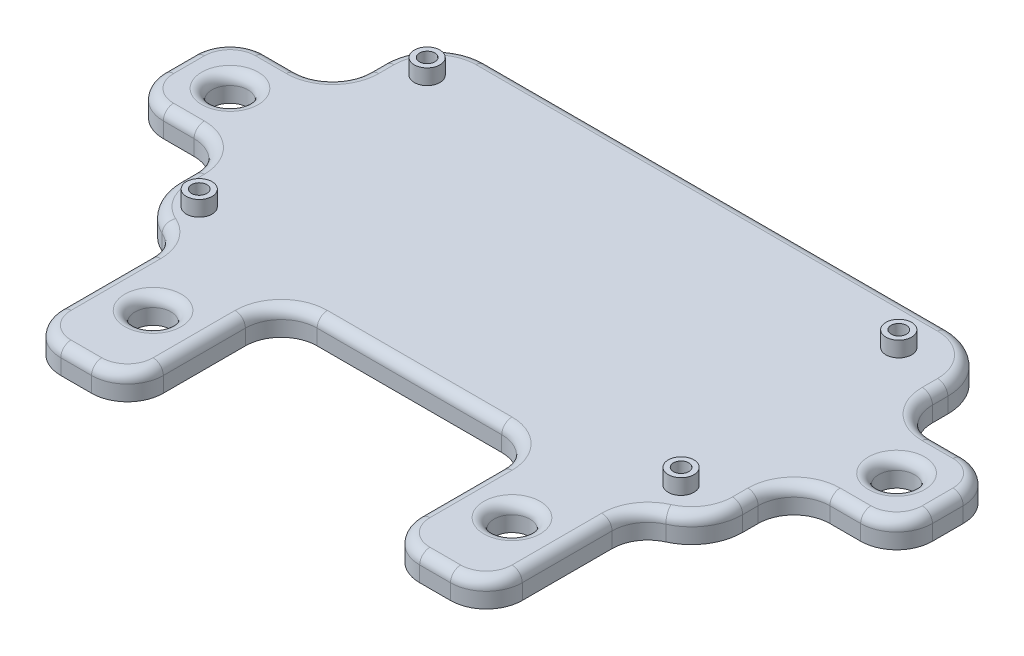
SolidWorks part; units mm, degrees
ref_plane "Front Plane" through (0, 0, 0) normal (0, 0, 1) x (1, 0, 0)
ref_plane "Top Plane" through (0, 0, 0) normal (0, 1, 0) x (1, 0, 0)
ref_plane "Right Plane" through (0, 0, 0) normal (1, 0, 0) x (0, 0, -1)
sketch "Sketch1" plane through (0, 0, 0) normal (0, 1, 0) x (1, 0, 0)
  line L1 (-49.43, 40.0745) -> (60.57, 40.0745)
  line L2 (-49.43, 40.0745) -> (-49.43, -19.9255)
  line L3 (-49.43, -19.9255) -> (60.57, -19.9255)
  line L4 (60.57, 40.0745) -> (60.57, -19.9255)
  dimension "D1" = 60
  dimension "D2" = 110
extrude "Boss-Extrude1" add sketch "Sketch1" along normal blind 5
sketch "Sketch2" plane through (0, 5, 0) normal (0, 1, 0) x (1, 0, 0)
  line L0 (-49.43, -19.9255) -> (60.57, -19.9255) construction
  line L1 (-49.43, 40.0745) -> (-49.43, -19.9255) construction
  circle A0 centre (-42.43, 31.5245) radius 1.0922
  circle A1 centre (-42.43, -12.9255) radius 1.0922
  circle A2 centre (51.55, -12.9255) radius 1.0922
  circle A3 centre (49.55, 31.5245) radius 1.0922
  dimension "D4" = 2.1844
  dimension "D5" = 93.98
  dimension "D1" = 44.45
  dimension "D2" = 7
  dimension "D3" = 7
extrude "Cut-Extrude1" cut sketch "Sketch2" against normal blind 10
sketch "Sketch3" plane through (0, 5, 0) normal (0, 1, 0) x (1, 0, 0)
  circle A0 centre (-42.43, 31.5245) radius 2.5
  circle A1 centre (-42.43, -12.9255) radius 2.5
  circle A2 centre (51.55, -12.9255) radius 2.5
  circle A3 centre (49.55, 31.5245) radius 2.5
  dimension "D1" = 5
extrude "Boss-Extrude2" add sketch "Sketch3" along normal blind 3
sketch "Sketch4" plane through (0, 8, 0) normal (0, 1, 0) x (1, 0, 0)
  circle A0 centre (-42.43, 31.5245) radius 1.5
  circle A1 centre (49.55, 31.5245) radius 1.5
  circle A2 centre (51.55, -12.9255) radius 1.5
  circle A3 centre (-42.43, -12.9255) radius 1.5
  dimension "D1" = 3
extrude "Cut-Extrude2" cut sketch "Sketch4" against normal blind 3
sketch "Sketch5" plane through (60.57, 0, 0) normal (1, 0, 0) x (0, 0, -1)
  line L0 (10.0745, 5) -> (10.0745, 0) construction
  line L1 (-19.9255, 5) -> (40.0745, 5) construction
  line L2 (-19.9255, 0) -> (40.0745, 0) construction
  line L4 (0.0745, 5) -> (20.0745, 5)
  line L5 (0.0745, 5) -> (0.0745, 0)
  line L6 (0.0745, 0) -> (20.0745, 0)
  line L7 (20.0745, 5) -> (20.0745, 0)
  line L8 (0.0745, 5) -> (20.0745, 0) construction
  line L9 (0.0745, 0) -> (20.0745, 5) construction
  point P6 (10.0745, 2.5)
  dimension "D1" = 20
extrude "Boss-Extrude3" add sketch "Sketch5" along normal blind 20 and the other way blind 130
sketch "Sketch6" plane through (0, 5, 0) normal (0, 1, 0) x (1, 0, 0)
  line L0 (-69.43, 10.0745) -> (80.57, 10.0745) construction
  line L1 (-69.43, 20.0745) -> (-69.43, 0.0745) construction
  line L2 (80.57, 20.0745) -> (80.57, 0.0745) construction
  circle A0 centre (-59.43, 10.0745) radius 3.5
  circle A1 centre (70.57, 10.0745) radius 3.5
  dimension "D3" = 7
  dimension "D1" = 10
  dimension "D2" = 10
extrude "Cut-Extrude3" cut sketch "Sketch6" against normal blind 20
sketch "Sketch7" plane through (0, 0, 19.9255) normal (0, 0, 1) x (1, 0, 0)
  line L0 (-49.43, 2.5) -> (60.57, 2.5) construction
  line L1 (-49.43, 5) -> (-49.43, 0) construction
  line L2 (60.57, 5) -> (60.57, 0) construction
  line L3 (5.57, 5) -> (5.57, 0) construction
  line L4 (-49.43, 5) -> (60.57, 5) construction
  line L5 (-49.43, 0) -> (60.57, 0) construction
  line L7 (-39.43, 5) -> (-19.43, 5)
  line L8 (-39.43, 5) -> (-39.43, 0)
  line L9 (-39.43, 0) -> (-19.43, 0)
  line L10 (-19.43, 5) -> (-19.43, 0)
  line L11 (-39.43, 5) -> (-19.43, 0) construction
  line L12 (-39.43, 0) -> (-19.43, 5) construction
  line L13 (30.57, 5) -> (50.57, 5)
  line L14 (30.57, 5) -> (30.57, 0)
  line L15 (30.57, 0) -> (50.57, 0)
  line L16 (50.57, 5) -> (50.57, 0)
  line L17 (30.57, 5) -> (50.57, 0) construction
  line L18 (30.57, 0) -> (50.57, 5) construction
  point P12 (-29.43, 2.5)
  point P17 (40.57, 2.5)
  dimension "D1" = 20
  dimension "D2" = 20
  dimension "D3" = 35
  dimension "D4" = 35
extrude "Boss-Extrude4" add sketch "Sketch7" along normal blind 30
sketch "Sketch8" plane through (0, 5, 0) normal (0, 1, 0) x (1, 0, 0)
  line L0 (50.57, -34.9255) -> (-39.43, -34.9255) construction
  line L1 (50.57, -49.9255) -> (50.57, -19.9255) construction
  line L2 (-39.43, -49.9255) -> (-39.43, -19.9255) construction
  line L3 (-29.43, -49.9255) -> (-29.43, -5.7984) construction
  line L4 (-19.43, -49.9255) -> (-39.43, -49.9255) construction
  line L5 (40.57, -49.9255) -> (40.57, -1.6081) construction
  line L6 (50.57, -49.9255) -> (30.57, -49.9255) construction
  circle A0 centre (-29.43, -34.9255) radius 3.5
  circle A1 centre (40.57, -34.9255) radius 3.5
  dimension "D1" = 7
extrude "Cut-Extrude4" cut sketch "Sketch8" against normal blind 30
fillet "Fillet1" radius 10 4 edges at (-49.43, 2.5, 19.9255) (-49.43, 2.5, -40.0745) (60.57, 2.5, -40.0745) (60.57, 2.5, 19.9255)
fillet "Fillet2" radius 7 8 edges at (60.57, 2.5, -20.0745) (60.57, 2.5, -0.0745) (-49.43, 2.5, -0.0745) (-49.43, 2.5, -20.0745) (-69.43, 2.5, -20.0745) (-69.43, 2.5, -0.0745) (80.57, 2.5, -20.0745) (80.57, 2.5, -0.0745)
fillet "Fillet3" radius 7 8 edges at (30.57, 2.5, 19.9255) (50.57, 2.5, 19.9255) (50.57, 2.5, 49.9255) (30.57, 2.5, 49.9255) (-19.43, 2.5, 49.9255) (-39.43, 2.5, 49.9255)
fillet "Fillet4" radius 2 38 edges at (-17.3797, 5, 21.9757) (-21.4802, 5, 47.8752) (-29.43, 5, 49.9255) (-37.3797, 5, 47.8752) (-40.5488, 5, 21.6211) (-49.43, 5, 8.4255) (-51.4802, 5, 1.9757) (-59.43, 5, -0.0745) (-67.3797, 5, -2.1248) (-69.43, 5, -10.0745) (-67.3797, 5, -18.0243) (-59.43, 5, -20.0745) (-51.4802, 5, -22.1248) (-49.43, 5, -28.5745) (-46.501, 5, -37.1456) (5.57, 5, -40.0745) (57.6411, 5, -37.1456) (60.57, 5, -28.5745) (62.6203, 5, -22.1248) (70.57, 5, -20.0745) (78.5198, 5, -18.0243) (80.57, 5, -10.0745) (78.5198, 5, -2.1248) (70.57, 5, -0.0745) (62.6203, 5, 1.9757) (60.57, 5, 8.4255) (58.9717, 5, 15.3488) (51.6889, 5, 21.6211) (50.57, 5, 34.1715) (48.5198, 5, 47.8752) (40.57, 5, 49.9255) (32.6203, 5, 47.8752) (30.57, 5, 34.9255) (28.5198, 5, 21.9757)
fillet "Fillet5" radius 2 2 edges at (70.57, 5, -6.5745) (-59.43, 5, -6.5745)
fillet "Fillet6" radius 2 2 edges at (40.57, 5, 38.4255) (-29.43, 5, 38.4255)
